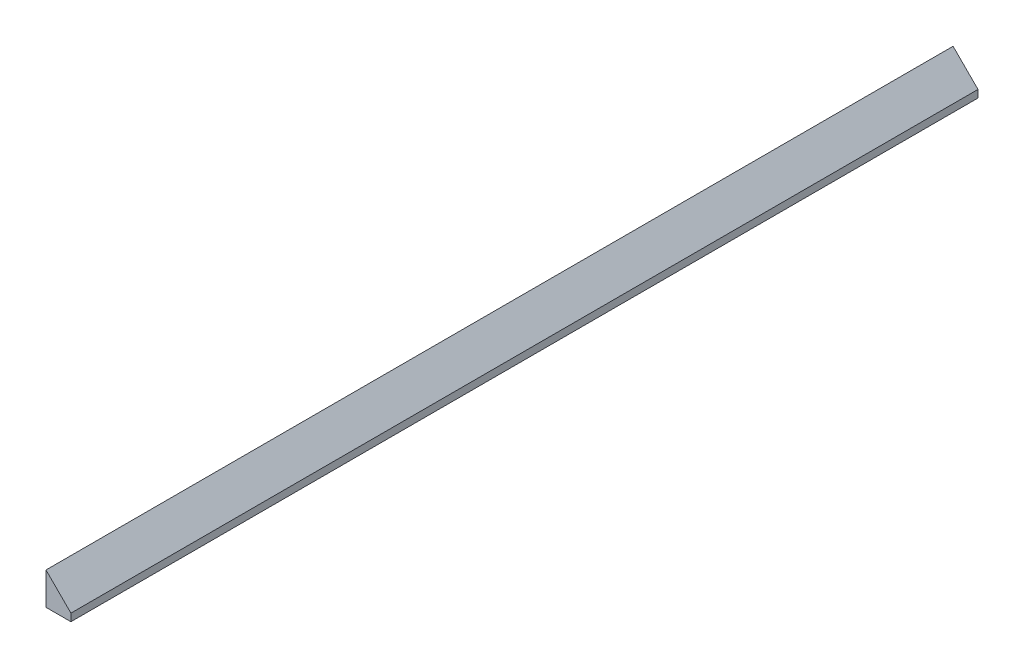
SolidWorks part; units mm, degrees
material "6061-T6 (SS)"
ref_plane "Front Plane" through (0, 0, 0) normal (0, 0, 1) x (1, 0, 0)
ref_plane "Top Plane" through (0, 0, 0) normal (0, 1, 0) x (1, 0, 0)
ref_plane "Right Plane" through (0, 0, 0) normal (1, 0, 0) x (0, 0, -1)
sketch "Sketch1" plane through (0, 0, 0) normal (0, 0, 1) x (1, 0, 0)
  line L5 (0, 0) -> (2.6, 0)
  line L6 (2.6, 0) -> (0, 2.6)
  line L7 (0, 2.6) -> (0, 0)
  line L11 (2, 0) -> (2, 0.6)
  dimension "D1" = 0.6
  dimension "D2" = 2.6
extrude "Boss-Extrude1" add sketch "Sketch1" against normal mid plane 72.8 contours L5 L11 L6 L7 region at (0.7917, 0.9042, 0)
sketch "Sketch2" [suppressed] plane through (0, 0, 0) normal (0, -1, 0) x (1, 0, 0)
  circle A6 centre (2.5, 0) radius 1 construction
  circle A7 centre (2.5, 0) radius 1
  circle A8 centre (2.5, -22) radius 1 construction
  circle A9 centre (2.5, -22) radius 1
  circle A10 centre (2.5, 22) radius 1 construction
  circle A11 centre (2.5, 22) radius 1
extrude "Cut-Extrude1" [suppressed] cut sketch "Sketch2" against normal up to surface (0.1 mm away) up to face at (1, 1.6, 0)
